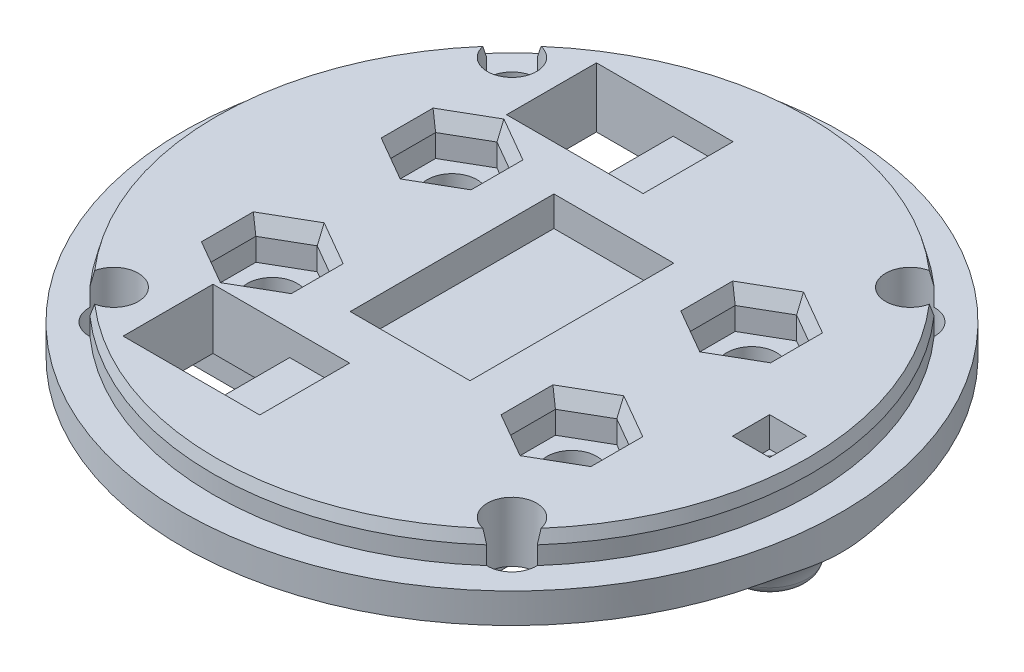
SolidWorks part; units mm, degrees
ref_plane "Спереди" through (0, 0, 0) normal (0, 0, 1) x (1, 0, 0)
ref_plane "Сверху" through (0, 0, 0) normal (0, 1, 0) x (1, 0, 0)
ref_plane "Справа" through (0, 0, 0) normal (1, 0, 0) x (0, 0, -1)
sketch "Эскиз1" plane through (0, 0, 0) normal (0, 1, 0) x (1, 0, 0)
  circle A0 centre (0, 0) radius 55
  dimension "D1" = 110
extrude "Бобышка-Вытянуть1" add sketch "Эскиз1" along normal blind 5
sketch "Эскиз2" plane through (0, 5, 0) normal (0, 1, 0) x (1, 0, 0)
  circle A0 centre (0, 0) radius 49.9
  dimension "D1" = 99.8
extrude "Бобышка-Вытянуть2" add sketch "Эскиз2" along normal blind 5
sketch "Эскиз3" plane through (0, 0, 0) normal (0, -1, 0) x (1, 0, 0)
  line L1 (17.5, -22.5) -> (-17.5, -22.5)
  line L2 (17.5, -22.5) -> (17.5, 22.5)
  line L3 (17.5, 22.5) -> (-17.5, 22.5)
  line L4 (-17.5, -22.5) -> (-17.5, 22.5)
  line L5 (17.5, -22.5) -> (-17.5, 22.5) construction
  line L6 (17.5, 22.5) -> (-17.5, -22.5) construction
  point P0 (0, 0)
  dimension "D1" = 35
  dimension "D2" = 45
extrude "Бобышка-Вытянуть3" add sketch "Эскиз3" along normal blind 25
sketch "Эскиз4" plane through (0, 0, 22.5) normal (0, 0, 1) x (1, 0, 0)
  line L0 (-17.5, 0) -> (17.5, -25) construction
  line L2 (10.1, -17.65) -> (-10.1, -17.65)
  line L3 (10.1, -17.65) -> (10.1, -7.35)
  line L4 (10.1, -7.35) -> (-10.1, -7.35)
  line L5 (-10.1, -17.65) -> (-10.1, -7.35)
  line L6 (10.1, -17.65) -> (-10.1, -7.35) construction
  line L7 (10.1, -7.35) -> (-10.1, -17.65) construction
  point P4 (0, -12.5)
  dimension "D1" = 20.2
  dimension "D2" = 10.3
extrude "Вырез-Вытянуть1" cut sketch "Эскиз4" against normal through all
sketch "Эскиз5" plane through (0, 0, 0) normal (0, -1, 0) x (1, 0, 0)
  line L1 (17.5, -22.5) -> (17.5, 22.5) construction
  line L2 (-33.234, -33.234) -> (33.234, -33.234) construction
  line L3 (-33.234, -33.234) -> (-33.234, 33.234) construction
  line L4 (-33.234, 33.234) -> (33.234, 33.234) construction
  line L10 (33.234, -33.234) -> (33.234, 33.234) construction
  circle A1 centre (33.234, -33.234) radius 4.1
  circle A2 centre (-33.234, -33.234) radius 4.1
  circle A3 centre (-33.234, 33.234) radius 4.1
  circle A4 centre (33.234, 33.234) radius 4.1
  circle A5 centre (0, 0) radius 47 construction
  point P0 (0, 0)
  dimension "D3" = 8.2
  dimension "D2" = 94
extrude "Вырез-Вытянуть2" cut sketch "Эскиз5" against normal through all
sketch "Эскиз6" plane through (0, 10, 0) normal (0, 1, 0) x (1, 0, 0)
  line L0 (0, 0) -> (0, 49.9) construction
  line L1 (0, 28) -> (-18, 28) construction
  arc A0 (33.1107, 37.3322) -> (-33.1107, 37.3322) centre (0, 0) ccw construction
  circle A1 centre (-18, 28) radius 2.75
  dimension "D3" = 5.5
  dimension "D1" = 28
  dimension "D2" = 18
extrude "Вырез-Вытянуть3" cut sketch "Эскиз6" against normal through all
chamfer "Chamfer1" distance 2 angle 15 4 edges at (0, 10, 49.9) (-49.9, 10, 0) (0, 10, -49.9) (49.9, 10, 0) first distance on face at (0, 7.5, 43.6161) first distance on face at (-43.6161, 7.5, 0) first distance on face at (0, 7.5, -43.6161) first distance on face at (43.6161, 7.5, 0)
sketch "Sketch2" plane through (0, -25, 0) normal (0, -1, 0) x (1, 0, 0)
  line L0 (17.5, 0) -> (-17.5652, 0) construction
  line L1 (17.5, -22.5) -> (17.5, 22.5) construction
  line L4 (-17.5652, -22.5) -> (17.5, -22.5)
  line L5 (-17.5652, -22.5) -> (-17.5652, 22.5)
  line L6 (-17.5652, 22.5) -> (17.5, 22.5)
  line L7 (17.5, -22.5) -> (17.5, 22.5)
  line L8 (-17.5652, -22.5) -> (17.5, 22.5) construction
  line L9 (-17.5652, 22.5) -> (17.5, -22.5) construction
  point P6 (-0.0326, 0)
extrude "Cut-Extrude1" cut sketch "Sketch2" against normal blind 12.5
sketch "Sketch4" plane through (0, -7.35, 0) normal (0, -1, 0) x (1, 0, 0)
  line L1 (-35, -22.5) -> (35, -22.5)
  line L2 (-35, -22.5) -> (-35, 22.5)
  line L3 (-35, 22.5) -> (35, 22.5)
  line L4 (35, -22.5) -> (35, 22.5)
  line L5 (-35, -22.5) -> (35, 22.5) construction
  line L6 (-35, 22.5) -> (35, -22.5) construction
  point P0 (0, 0)
  dimension "D1" = 45
  dimension "D2" = 70
extrude "Boss-Extrude1" add sketch "Sketch4" against normal up to surface (7.35 mm away) from offset 2 up to face at (-18, 0, -25.25) offset against normal yes
sketch "Sketch5" plane through (0, -5.35, 0) normal (0, -1, 0) x (1, 0, 0)
  line L0 (25, 22.5) -> (25, -22.5) construction
  line L1 (35, 22.5) -> (17.5, 22.5) construction
  line L2 (17.5, -22.5) -> (35, -22.5) construction
  line L3 (-25, 22.5) -> (-25, -22.5) construction
  line L4 (-17.5, 22.5) -> (-35, 22.5) construction
  line L5 (-35, -22.5) -> (-17.5, -22.5) construction
  line L6 (25, 15) -> (-25, 15) construction
  line L7 (25, -15) -> (-25, -15) construction
  circle A0 centre (25, 15) radius 4.15
  circle A1 centre (-25, 15) radius 4.15
  circle A2 centre (25, -15) radius 4.15
  circle A3 centre (-25, -15) radius 4.15
  point P21 (25, 0)
  dimension "D1" = 8.3
  dimension "D2" = 50
  dimension "D3" = 25
  dimension "D4" = 30
  dimension "D5" = 15
extrude "Cut-Extrude2" cut sketch "Sketch5" against normal through all
sketch "Sketch6" plane through (0, 10, 0) normal (0, 1, 0) x (1, 0, 0)
  line L1 (-18.5048, -11.25) -> (-25, -7.5)
  line L2 (-25, -7.5) -> (-31.4952, -11.25)
  line L3 (-31.4952, -11.25) -> (-31.4952, -18.75)
  line L4 (-31.4952, -18.75) -> (-25, -22.5)
  line L5 (-25, -22.5) -> (-18.5048, -18.75)
  line L6 (-18.5048, -18.75) -> (-18.5048, -11.25)
  line L7 (31.4952, -11.25) -> (25, -7.5)
  line L8 (25, -7.5) -> (18.5048, -11.25)
  line L9 (18.5048, -11.25) -> (18.5048, -18.75)
  line L10 (18.5048, -18.75) -> (25, -22.5)
  line L11 (25, -22.5) -> (31.4952, -18.75)
  line L12 (31.4952, -18.75) -> (31.4952, -11.25)
  line L13 (31.4952, 18.75) -> (25, 22.5)
  line L14 (25, 22.5) -> (18.5048, 18.75)
  line L15 (18.5048, 18.75) -> (18.5048, 11.25)
  line L16 (18.5048, 11.25) -> (25, 7.5)
  line L17 (25, 7.5) -> (31.4952, 11.25)
  line L18 (31.4952, 11.25) -> (31.4952, 18.75)
  line L19 (-18.5048, 18.75) -> (-25, 22.5)
  line L20 (-25, 22.5) -> (-31.4952, 18.75)
  line L21 (-31.4952, 18.75) -> (-31.4952, 11.25)
  line L22 (-31.4952, 11.25) -> (-25, 7.5)
  line L23 (-25, 7.5) -> (-18.5048, 11.25)
  line L24 (-18.5048, 11.25) -> (-18.5048, 18.75)
  circle A0 centre (-25, -15) radius 7.5 construction
  circle A1 centre (25, -15) radius 7.5 construction
  circle A2 centre (25, 15) radius 7.5 construction
  circle A3 centre (-25, 15) radius 7.5 construction
  dimension "D1" = 15
extrude "Cut-Extrude3" cut sketch "Sketch6" against normal blind 6.5
sketch "Sketch7" plane through (0, 10, 0) normal (0, 1, 0) x (1, 0, 0)
  line L1 (-10, -17) -> (10, -17)
  line L2 (-10, -17) -> (-10, 17)
  line L3 (-10, 17) -> (10, 17)
  line L4 (10, -17) -> (10, 17)
  line L5 (-10, -17) -> (10, 17) construction
  line L6 (-10, 17) -> (10, -17) construction
  point P0 (0, 0)
  dimension "D1" = 20
  dimension "D2" = 34
extrude "Cut-Extrude4" cut sketch "Sketch7" against normal blind 5
chamfer "Chamfer2" distance 1 angle 70 24 edges at (-28.2476, 10, 9.375) (-31.4952, 10, 15) (-28.2476, 10, 20.625) (-21.7524, 10, 20.625) (-18.5048, 10, 15) (-21.7524, 10, 9.375) (18.5048, 10, 15) (21.7524, 10, 20.625) (28.2476, 10, 20.625) (31.4952, 10, 15) (28.2476, 10, 9.375) (21.7524, 10, 9.375) (-28.2476, 10, -9.375) (-31.4952, 10, -15) (-28.2476, 10, -20.625) (-21.7524, 10, -20.625) (-18.5048, 10, -15) (-21.7524, 10, -9.375) (21.7524, 10, -9.375) (18.5048, 10, -15) (21.7524, 10, -20.625) (28.2476, 10, -20.625) (31.4952, 10, -15) (28.2476, 10, -9.375) first distance on face at (0, 10, 0)
sketch "Sketch8" plane through (0, 0, 0) normal (0, -1, 0) x (1, 0, 0)
  line L0 (-35, 0) -> (-55, 0) construction
  line L1 (-35, 22.5) -> (-35, -22.5) construction
  line L2 (-35, 0) -> (55, 0) construction
  circle A0 centre (0, 0) radius 55 construction
  circle A1 centre (43, 0) radius 2.1
  dimension "D1" = 4.2
  dimension "D2" = 12
extrude "Cut-Extrude5" cut sketch "Sketch8" against normal through all draft 2 draft outward yes
sketch "Sketch9" plane through (0, 10, 0) normal (0, 1, 0) x (1, 0, 0)
  line L1 (39.9, -3.1) -> (46.1, -3.1)
  line L2 (39.9, -3.1) -> (39.9, 3.1)
  line L3 (39.9, 3.1) -> (46.1, 3.1)
  line L4 (46.1, -3.1) -> (46.1, 3.1)
  line L5 (39.9, -3.1) -> (46.1, 3.1) construction
  line L6 (39.9, 3.1) -> (46.1, -3.1) construction
  point P0 (43, 0)
  dimension "D1" = 6.2
extrude "Cut-Extrude6" cut sketch "Sketch9" against normal blind 5
chamfer "Chamfer3" distance 0.7 angle 70 1 edges at (43, 5, -2.2746) first distance on face at (43, 5, 0)
sketch "Sketch10" plane through (0, 0, 0) normal (0, -1, 0) x (1, 0, 0)
  circle A0 centre (43, 0) radius 6
  circle A1 centre (43, 0) radius 3
  dimension "D1" = 6
  dimension "D2" = 12
extrude "Boss-Extrude2" add sketch "Sketch10" along normal blind 9
fillet "Fillet1" radius 10 1 edges at (43, 0, 6)
fillet "Fillet2" radius 2 1 edges at (43, -9, -6)
sketch "Sketch11" plane through (0, 0, 0) normal (0, -1, 0) x (1, 0, 0)
  line L0 (-19, -51.614) -> (-19, 51.614) construction
  line L2 (-25.4, -39.5) -> (-12.6, -39.5)
  line L3 (-25.4, -39.5) -> (-25.4, -24.5)
  line L4 (-25.4, -24.5) -> (-12.6, -24.5)
  line L5 (-12.6, -39.5) -> (-12.6, -24.5)
  line L6 (-25.4, -39.5) -> (-12.6, -24.5) construction
  line L7 (-25.4, -24.5) -> (-12.6, -39.5) construction
  line L8 (-25.4, 39.5) -> (-12.6, 39.5)
  line L9 (-25.4, 39.5) -> (-25.4, 24.5)
  line L10 (-25.4, 24.5) -> (-12.6, 24.5)
  line L11 (-12.6, 39.5) -> (-12.6, 24.5)
  line L12 (-25.4, 39.5) -> (-12.6, 24.5) construction
  line L13 (-25.4, 24.5) -> (-12.6, 39.5) construction
  circle A0 centre (-33.234, -33.234) radius 7.5 construction
  arc A1 (53.7163, 11.8135) -> (53.7163, -11.8135) centre (0, 0) ccw construction
  point P2 (-19, 32)
  point P9 (-19, -32)
  point P14 (-19, 0)
  dimension "D1" = 15
  dimension "D2" = 15
  dimension "D3" = 12.8
  dimension "D4" = 19
  dimension "D5" = 32
  dimension "D6" = 32
extrude "Cut-Extrude7" cut sketch "Sketch11" against normal through all
sketch "Sketch13" plane through (0, 10, 0) normal (0, 1, 0) x (1, 0, 0)
  line L0 (-12.6, 39.5) -> (-2.6, 39.5)
  line L1 (-2.6, 39.5) -> (-2.6, 24.5)
  line L2 (-2.6, 24.5) -> (-12.6, 24.5)
  line L3 (-12.6, 24.5) -> (-12.6, 39.5)
  line L4 (-12.6, -24.5) -> (-2.6, -24.5)
  line L5 (-2.6, -24.5) -> (-2.6, -39.5)
  line L6 (-2.6, -39.5) -> (-12.6, -39.5)
  line L7 (-12.6, -24.5) -> (-12.6, -39.5)
  dimension "D1" = 10
extrude "Cut-Extrude8" cut sketch "Sketch13" against normal offset from surface (4.2 mm away) 5.8 up to face at (-19, 0, 32)
